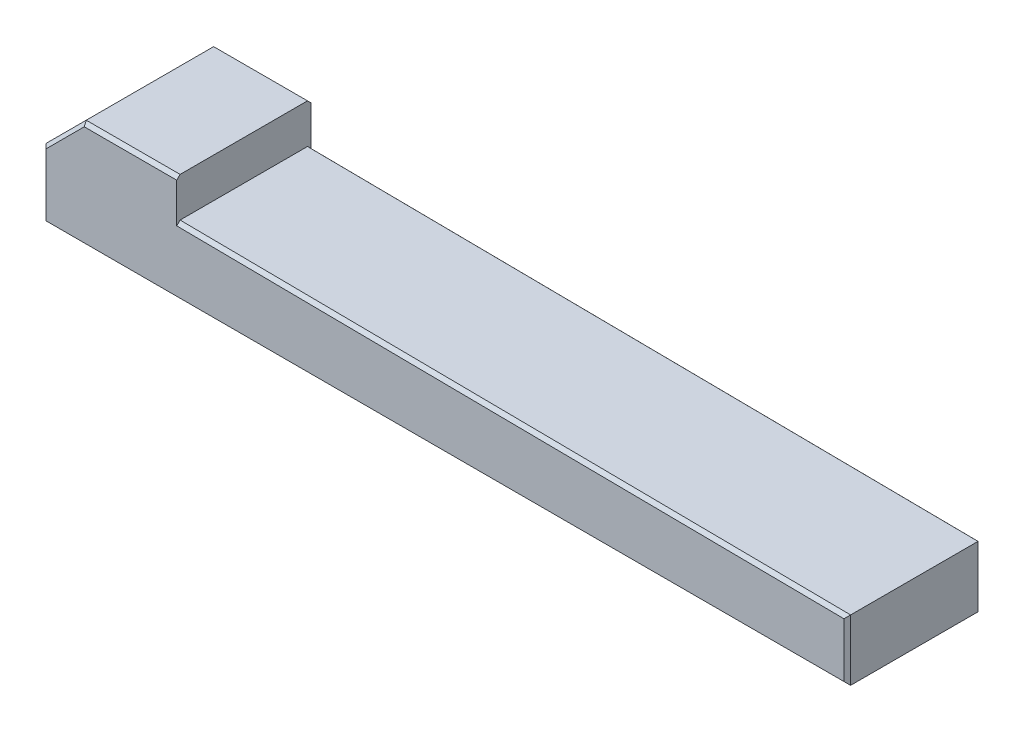
SolidWorks part; units mm, degrees
ref_plane "Front" through (0, 0, 0) normal (0, 0, 1) x (1, 0, 0)
ref_plane "Top" through (0, 0, 0) normal (0, 1, 0) x (1, 0, 0)
ref_plane "Right" through (0, 0, 0) normal (1, 0, 0) x (0, 0, -1)
sketch "Sketch1" plane through (0, 0, 0) normal (0, 0, 1) x (1, 0, 0)
  line L0 (0, 0) -> (600, 0)
  line L1 (600, 0) -> (600, 45.4995)
  line L2 (600, 45.4995) -> (100, 50.5001)
  line L3 (100, 50.5001) -> (100, 80)
  line L4 (100, 80) -> (30, 80)
  line L5 (30, 80) -> (0, 50)
  line L6 (0, 50) -> (0, 0)
  point P8 (150, 50)
  dimension "D6" = 50
  dimension "D7" = 50
  dimension "D8" = 0.573
extrude "BaseKey" add sketch "Sketch1" along normal mid plane 100
chamfer "Chamfer1" distance 2.5 angle 45 12 edges at (65, 80, -50) (15, 65, -50) (0, 25, -50) (300, 0, -50) (600, 22.7498, -50) (350, 47.9998, -50) (0, 25, 50) (15, 65, 50) (65, 80, 50) (300, 0, 50) (600, 22.7498, 50) (350, 47.9998, 50)
equation "\"D7@Sketch1\" = \"h@Sketch1\""
equation "\"D6@Sketch1\" = \"h@Sketch1\""
equation "\"D1@BaseKey\" = \"b@Sketch1\""
